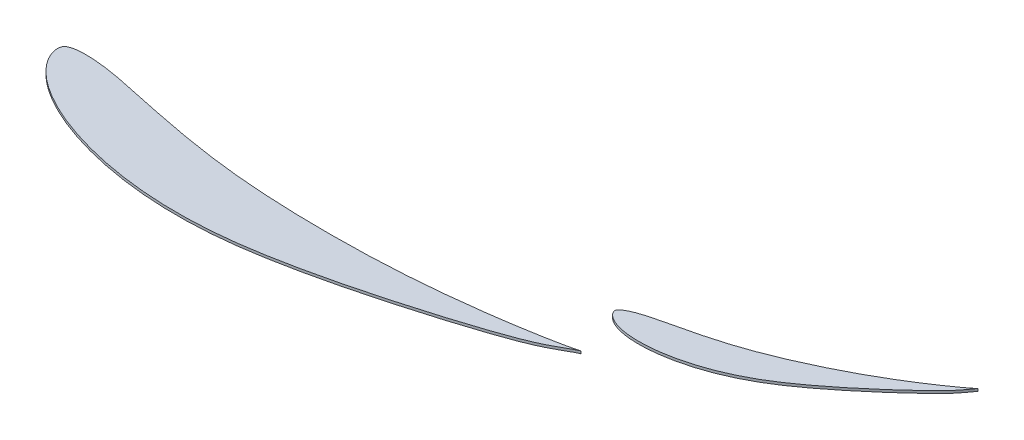
SolidWorks part; units mm, degrees
ref_plane "Front Plane" through (0, 0, 0) normal (0, 0, 1) x (1, 0, 0)
ref_plane "Top Plane" through (0, 0, 0) normal (0, 1, 0) x (1, 0, 0)
ref_plane "Right Plane" through (0, 0, 0) normal (1, 0, 0) x (0, 0, -1)
sketch "Sketch1" plane through (0, 0, 0) normal (0, 1, 0) x (1, 0, 0)
  spline S0 degree 3 poles (-69.7235, 37.8267) (-64.4975, 39.4817) (-69.3304, 37.4567) (-72.8148, 35.4) (-80.7227, 31.0375) (-89.8687, 26.058) (-101.6654, 20.7446) (-115.6887, 15.4124) (-131.9838, 9.7388) (-150.3138, 3.7512) (-170.4203, -2.4732) (-192.0007, -8.832) (-214.756, -15.1807) (-238.3766, -21.3821) (-262.5602, -27.2669) (-287.0162, -32.6385) (-311.4568, -37.3302) (-335.6828, -41.1008) (-359.5919, -43.6132) (-383.094, -44.823) (-406.1048, -44.7568) (-428.5003, -43.4674) (-450.1498, -41.0172) (-470.8999, -37.4937) (-490.597, -33.0546) (-509.0649, -27.8126) (-526.1291, -21.8663) (-541.6405, -15.3345) (-555.4661, -8.3369) (-567.501, -1.005) (-577.6561, 6.5208) (-585.8772, 14.0826) (-592.1333, 21.4997) (-596.4095, 28.5906) (-598.575, 34.6968) (-599.036, 38.9119) (-598.7904, 41.1263) (-598.5559, 42.2073) (-598.3073, 42.9095) (-598.0806, 43.4311) (-597.8794, 43.7859) (-597.6525, 44.1159) (-597.3684, 44.4079) (-597.0458, 44.6816) (-596.5563, 45.0558) (-595.837, 45.4763) (-594.6855, 46.0337) (-593.2668, 46.5595) (-589.5244, 47.655) (-582.5582, 48.4203) (-571.539, 48.2683) (-557.6787, 46.8029) (-540.9024, 44.032) (-521.0437, 39.934) (-497.9754, 34.8534) (-471.6859, 29.5034) (-442.4873, 24.3683) (-410.9191, 19.9029) (-377.6985, 16.6962) (-343.6903, 14.8703) (-309.6629, 14.1027) (-276.183, 14.2641) (-243.7578, 15.3066) (-212.9263, 17.2261) (-184.2105, 19.8361) (-158.0453, 22.8332) (-134.7326, 26.0011) (-114.6103, 29.1294) (-97.6267, 32.0949) (-84.6293, 34.5236) (-74.1006, 36.918) (-69.7235, 37.8267) (-64.4975, 39.4817) (-69.3304, 37.4567) knots -0.016237 -0.007308 -0.001841 0 0.001813 0.006911 0.014576 0.024172 0.035572 0.049013 0.064513 0.081849 0.100772 0.120997 0.142228 0.164173 0.186537 0.209023 0.231367 0.25332 0.274804 0.295858 0.316449 0.336531 0.356033 0.374893 0.39299 0.410197 0.426388 0.441459 0.455334 0.467938 0.479236 0.489204 0.497851 0.505194 0.511308 0.515097 0.516441 0.517273 0.51806 0.518436 0.518797 0.519154 0.519508 0.519887 0.520289 0.52116 0.522116 0.52372 0.525214 0.532575 0.542381 0.554776 0.569931 0.588005 0.609188 0.633329 0.660001 0.688743 0.718873 0.749543 0.780127 0.810209 0.839387 0.867183 0.893104 0.91676 0.937874 0.956199 0.971544 0.983763 0.992692 0.998159 1 1.001813 1.006911 1.014576 only from (-65.525, 39.1038) to (-65.525, 39.1038)
  spline S1 degree 3 poles (168.0228, 206.4477) (170.1374, 208.3902) (168.2914, 206.359) (167.0925, 204.6113) (164.3041, 200.7897) (161.0645, 196.4011) (156.6404, 191.2672) (151.1635, 185.6315) (144.6837, 179.3308) (137.3073, 172.4305) (129.14, 165.0246) (120.3027, 157.2285) (110.9055, 149.1773) (101.0648, 141.0043) (90.8868, 132.857) (80.4659, 124.8931) (69.9017, 117.2554) (59.2355, 110.1024) (48.4413, 103.6169) (37.5519, 97.8399) (26.6132, 92.7774) (15.696, 88.4318) (4.8758, 84.8024) (-5.755, 81.8816) (-16.0885, 79.6286) (-26.0162, 78.0289) (-35.4335, 77.0743) (-44.2432, 76.7413) (-52.3557, 77.0027) (-59.6922, 77.8192) (-66.1791, 79.1439) (-71.7559, 80.9138) (-76.3679, 83.0501) (-79.9676, 85.4697) (-82.3474, 87.8891) (-83.4994, 89.7882) (-83.873, 90.8938) (-84.0009, 91.4589) (-84.0384, 91.8473) (-84.0462, 92.1451) (-84.0292, 92.358) (-83.9946, 92.5649) (-83.9243, 92.7664) (-83.8318, 92.9678) (-83.6822, 93.2538) (-83.4339, 93.6127) (-83.0106, 94.1322) (-82.4535, 94.6958) (-80.9194, 96.0444) (-77.7817, 97.9498) (-72.5169, 100.317) (-65.6125, 102.6896) (-57.0349, 105.088) (-46.7001, 107.5387) (-34.6241, 110.2334) (-20.9593, 113.5133) (-5.961, 117.5393) (10.0139, 122.4077) (26.4947, 128.2394) (43.0437, 134.9011) (59.3676, 142.0694) (75.2258, 149.5575) (90.3884, 157.2304) (104.6002, 164.9669) (117.6547, 172.5628) (129.4127, 179.7778) (139.7787, 186.4425) (148.6389, 192.3821) (156.0451, 197.5496) (161.6777, 201.5798) (166.146, 205.0473) (168.0228, 206.4477) (170.1374, 208.3902) (168.2914, 206.359) knots -0.016237 -0.007308 -0.001841 0 0.001813 0.006911 0.014576 0.024172 0.035572 0.049013 0.064513 0.081849 0.100772 0.120997 0.142228 0.164173 0.186537 0.209023 0.231367 0.25332 0.274804 0.295858 0.316449 0.336531 0.356033 0.374893 0.39299 0.410197 0.426388 0.441459 0.455334 0.467938 0.479236 0.489204 0.497851 0.505194 0.511308 0.515097 0.516441 0.517273 0.51806 0.518436 0.518797 0.519154 0.519508 0.519887 0.520289 0.52116 0.522116 0.52372 0.525214 0.532575 0.542381 0.554776 0.569931 0.588005 0.609188 0.633329 0.660001 0.688743 0.718873 0.749543 0.780127 0.810209 0.839387 0.867183 0.893104 0.91676 0.937874 0.956199 0.971544 0.983763 0.992692 0.998159 1 1.001813 1.006911 1.014576 only from (169.7332, 207.9834) to (169.7332, 207.9834)
  dimension "D1" = 169.7332
  dimension "D2" = 65.525
  dimension "D3" = 39.1038
  dimension "D4" = 207.9834
extrude "Boss-Extrude1" add sketch "Sketch1" along normal blind 2.54
sketch "Sketch2" plane through (0, 2.54, 0) normal (0, 1, 0) x (1, 0, 0)
  spline S0 degree 3 poles (-69.3304, 37.4567) (-64.4975, 39.4817) (-69.7235, 37.8267) (-74.1006, 36.918) (-84.6293, 34.5236) (-97.6267, 32.0949) (-114.6103, 29.1294) (-134.7326, 26.0011) (-158.0453, 22.8332) (-184.2105, 19.8361) (-212.9263, 17.2261) (-243.7578, 15.3066) (-276.183, 14.2641) (-309.6629, 14.1027) (-343.6903, 14.8703) (-377.6985, 16.6962) (-410.9191, 19.9029) (-442.4873, 24.3683) (-471.6859, 29.5034) (-497.9754, 34.8534) (-521.0437, 39.934) (-540.9024, 44.032) (-557.6787, 46.8029) (-571.539, 48.2683) (-582.5582, 48.4203) (-589.5244, 47.655) (-593.2668, 46.5595) (-594.6855, 46.0337) (-595.837, 45.4763) (-596.5563, 45.0558) (-597.0458, 44.6816) (-597.3684, 44.4079) (-597.6525, 44.1159) (-597.8794, 43.7859) (-598.0806, 43.4311) (-598.3073, 42.9095) (-598.5559, 42.2073) (-598.7904, 41.1263) (-599.036, 38.9119) (-598.575, 34.6968) (-596.4095, 28.5906) (-592.1333, 21.4997) (-585.8772, 14.0826) (-577.6561, 6.5208) (-567.501, -1.005) (-555.4661, -8.3369) (-541.6405, -15.3345) (-526.1291, -21.8663) (-509.0649, -27.8126) (-490.597, -33.0546) (-470.8999, -37.4937) (-450.1498, -41.0172) (-428.5003, -43.4674) (-406.1048, -44.7568) (-383.094, -44.823) (-359.5919, -43.6132) (-335.6828, -41.1008) (-311.4568, -37.3302) (-287.0162, -32.6385) (-262.5602, -27.2669) (-238.3766, -21.3821) (-214.756, -15.1807) (-192.0007, -8.832) (-170.4203, -2.4732) (-150.3138, 3.7512) (-131.9838, 9.7388) (-115.6887, 15.4124) (-101.6654, 20.7446) (-89.8687, 26.058) (-80.7227, 31.0375) (-72.8148, 35.4) (-69.3304, 37.4567) (-64.4975, 39.4817) (-69.7235, 37.8267) knots -0.014576 -0.006911 -0.001813 0 0.001841 0.007308 0.016237 0.028456 0.043801 0.062126 0.08324 0.106896 0.132817 0.160613 0.189791 0.219873 0.250457 0.281127 0.311257 0.339999 0.366671 0.390812 0.411995 0.430069 0.445224 0.457619 0.467425 0.474786 0.47628 0.477884 0.47884 0.479711 0.480113 0.480492 0.480846 0.481203 0.481564 0.48194 0.482727 0.483559 0.484903 0.488692 0.494806 0.502149 0.510796 0.520764 0.532062 0.544666 0.558541 0.573612 0.589803 0.60701 0.625107 0.643967 0.663469 0.683551 0.704142 0.725196 0.74668 0.768633 0.790977 0.813463 0.835827 0.857772 0.879003 0.899228 0.918151 0.935487 0.950987 0.964428 0.975828 0.985424 0.993089 0.998187 1 1.001841 1.007308 1.016237 only from (-65.525, 39.1038) to (-65.525, 39.1038) construction
  spline S1 degree 3 poles (-69.3304, 37.4567) (-64.4975, 39.4817) (-69.7235, 37.8267) (-74.1006, 36.918) (-84.6293, 34.5236) (-97.6267, 32.0949) (-114.6103, 29.1294) (-134.7326, 26.0011) (-158.0453, 22.8332) (-184.2105, 19.8361) (-212.9263, 17.2261) (-243.7578, 15.3066) (-276.183, 14.2641) (-309.6629, 14.1027) (-343.6903, 14.8703) (-377.6985, 16.6962) (-410.9191, 19.9029) (-442.4873, 24.3683) (-471.6859, 29.5034) (-497.9754, 34.8534) (-521.0437, 39.934) (-540.9024, 44.032) (-557.6787, 46.8029) (-571.539, 48.2683) (-582.5582, 48.4203) (-589.5244, 47.655) (-593.2668, 46.5595) (-594.6855, 46.0337) (-595.837, 45.4763) (-596.5563, 45.0558) (-597.0458, 44.6816) (-597.3684, 44.4079) (-597.6525, 44.1159) (-597.8794, 43.7859) (-598.0806, 43.4311) (-598.3073, 42.9095) (-598.5559, 42.2073) (-598.7904, 41.1263) (-599.036, 38.9119) (-598.575, 34.6968) (-596.4095, 28.5906) (-592.1333, 21.4997) (-585.8772, 14.0826) (-577.6561, 6.5208) (-567.501, -1.005) (-555.4661, -8.3369) (-541.6405, -15.3345) (-526.1291, -21.8663) (-509.0649, -27.8126) (-490.597, -33.0546) (-470.8999, -37.4937) (-450.1498, -41.0172) (-428.5003, -43.4674) (-406.1048, -44.7568) (-383.094, -44.823) (-359.5919, -43.6132) (-335.6828, -41.1008) (-311.4568, -37.3302) (-287.0162, -32.6385) (-262.5602, -27.2669) (-238.3766, -21.3821) (-214.756, -15.1807) (-192.0007, -8.832) (-170.4203, -2.4732) (-150.3138, 3.7512) (-131.9838, 9.7388) (-115.6887, 15.4124) (-101.6654, 20.7446) (-89.8687, 26.058) (-80.7227, 31.0375) (-72.8148, 35.4) (-69.3304, 37.4567) (-64.4975, 39.4817) (-69.7235, 37.8267) knots -0.014576 -0.006911 -0.001813 0 0.001841 0.007308 0.016237 0.028456 0.043801 0.062126 0.08324 0.106896 0.132817 0.160613 0.189791 0.219873 0.250457 0.281127 0.311257 0.339999 0.366671 0.390812 0.411995 0.430069 0.445224 0.457619 0.467425 0.474786 0.47628 0.477884 0.47884 0.479711 0.480113 0.480492 0.480846 0.481203 0.481564 0.48194 0.482727 0.483559 0.484903 0.488692 0.494806 0.502149 0.510796 0.520764 0.532062 0.544666 0.558541 0.573612 0.589803 0.60701 0.625107 0.643967 0.663469 0.683551 0.704142 0.725196 0.74668 0.768633 0.790977 0.813463 0.835827 0.857772 0.879003 0.899228 0.918151 0.935487 0.950987 0.964428 0.975828 0.985424 0.993089 0.998187 1 1.001841 1.007308 1.016237 only from (-65.525, 39.1038) to (-65.525, 39.1038)
  spline S3 degree 3 poles (168.2914, 206.359) (170.1374, 208.3902) (168.0228, 206.4477) (166.146, 205.0473) (161.6777, 201.5798) (156.0451, 197.5496) (148.6389, 192.3821) (139.7787, 186.4425) (129.4127, 179.7778) (117.6547, 172.5628) (104.6002, 164.9669) (90.3884, 157.2304) (75.2258, 149.5575) (59.3676, 142.0694) (43.0437, 134.9011) (26.4947, 128.2394) (10.0139, 122.4077) (-5.961, 117.5393) (-20.9593, 113.5133) (-34.6241, 110.2334) (-46.7001, 107.5387) (-57.0349, 105.088) (-65.6125, 102.6896) (-72.5169, 100.317) (-77.7817, 97.9498) (-80.9194, 96.0444) (-82.4535, 94.6958) (-83.0106, 94.1322) (-83.4339, 93.6127) (-83.6822, 93.2538) (-83.8318, 92.9678) (-83.9243, 92.7664) (-83.9946, 92.5649) (-84.0292, 92.358) (-84.0462, 92.1451) (-84.0384, 91.8473) (-84.0009, 91.4589) (-83.873, 90.8938) (-83.4994, 89.7882) (-82.3474, 87.8891) (-79.9676, 85.4697) (-76.3679, 83.0501) (-71.7559, 80.9138) (-66.1791, 79.1439) (-59.6922, 77.8192) (-52.3557, 77.0027) (-44.2432, 76.7413) (-35.4335, 77.0743) (-26.0162, 78.0289) (-16.0885, 79.6286) (-5.755, 81.8816) (4.8758, 84.8024) (15.696, 88.4318) (26.6132, 92.7774) (37.5519, 97.8399) (48.4413, 103.6169) (59.2355, 110.1024) (69.9017, 117.2554) (80.4659, 124.8931) (90.8868, 132.857) (101.0648, 141.0043) (110.9055, 149.1773) (120.3027, 157.2285) (129.14, 165.0246) (137.3073, 172.4305) (144.6837, 179.3308) (151.1635, 185.6315) (156.6404, 191.2672) (161.0645, 196.4011) (164.3041, 200.7897) (167.0925, 204.6113) (168.2914, 206.359) (170.1374, 208.3902) (168.0228, 206.4477) knots -0.014576 -0.006911 -0.001813 0 0.001841 0.007308 0.016237 0.028456 0.043801 0.062126 0.08324 0.106896 0.132817 0.160613 0.189791 0.219873 0.250457 0.281127 0.311257 0.339999 0.366671 0.390812 0.411995 0.430069 0.445224 0.457619 0.467425 0.474786 0.47628 0.477884 0.47884 0.479711 0.480113 0.480492 0.480846 0.481203 0.481564 0.48194 0.482727 0.483559 0.484903 0.488692 0.494806 0.502149 0.510796 0.520764 0.532062 0.544666 0.558541 0.573612 0.589803 0.60701 0.625107 0.643967 0.663469 0.683551 0.704142 0.725196 0.74668 0.768633 0.790977 0.813463 0.835827 0.857772 0.879003 0.899228 0.918151 0.935487 0.950987 0.964428 0.975828 0.985424 0.993089 0.998187 1 1.001841 1.007308 1.016237 only from (169.7332, 207.9834) to (169.7332, 207.9834)
  spline S4 degree 3 poles (168.2914, 206.359) (170.1374, 208.3902) (168.0228, 206.4477) (166.146, 205.0473) (161.6777, 201.5798) (156.0451, 197.5496) (148.6389, 192.3821) (139.7787, 186.4425) (129.4127, 179.7778) (117.6547, 172.5628) (104.6002, 164.9669) (90.3884, 157.2304) (75.2258, 149.5575) (59.3676, 142.0694) (43.0437, 134.9011) (26.4947, 128.2394) (10.0139, 122.4077) (-5.961, 117.5393) (-20.9593, 113.5133) (-34.6241, 110.2334) (-46.7001, 107.5387) (-57.0349, 105.088) (-65.6125, 102.6896) (-72.5169, 100.317) (-77.7817, 97.9498) (-80.9194, 96.0444) (-82.4535, 94.6958) (-83.0106, 94.1322) (-83.4339, 93.6127) (-83.6822, 93.2538) (-83.8318, 92.9678) (-83.9243, 92.7664) (-83.9946, 92.5649) (-84.0292, 92.358) (-84.0462, 92.1451) (-84.0384, 91.8473) (-84.0009, 91.4589) (-83.873, 90.8938) (-83.4994, 89.7882) (-82.3474, 87.8891) (-79.9676, 85.4697) (-76.3679, 83.0501) (-71.7559, 80.9138) (-66.1791, 79.1439) (-59.6922, 77.8192) (-52.3557, 77.0027) (-44.2432, 76.7413) (-35.4335, 77.0743) (-26.0162, 78.0289) (-16.0885, 79.6286) (-5.755, 81.8816) (4.8758, 84.8024) (15.696, 88.4318) (26.6132, 92.7774) (37.5519, 97.8399) (48.4413, 103.6169) (59.2355, 110.1024) (69.9017, 117.2554) (80.4659, 124.8931) (90.8868, 132.857) (101.0648, 141.0043) (110.9055, 149.1773) (120.3027, 157.2285) (129.14, 165.0246) (137.3073, 172.4305) (144.6837, 179.3308) (151.1635, 185.6315) (156.6404, 191.2672) (161.0645, 196.4011) (164.3041, 200.7897) (167.0925, 204.6113) (168.2914, 206.359) (170.1374, 208.3902) (168.0228, 206.4477) knots -0.014576 -0.006911 -0.001813 0 0.001841 0.007308 0.016237 0.028456 0.043801 0.062126 0.08324 0.106896 0.132817 0.160613 0.189791 0.219873 0.250457 0.281127 0.311257 0.339999 0.366671 0.390812 0.411995 0.430069 0.445224 0.457619 0.467425 0.474786 0.47628 0.477884 0.47884 0.479711 0.480113 0.480492 0.480846 0.481203 0.481564 0.48194 0.482727 0.483559 0.484903 0.488692 0.494806 0.502149 0.510796 0.520764 0.532062 0.544666 0.558541 0.573612 0.589803 0.60701 0.625107 0.643967 0.663469 0.683551 0.704142 0.725196 0.74668 0.768633 0.790977 0.813463 0.835827 0.857772 0.879003 0.899228 0.918151 0.935487 0.950987 0.964428 0.975828 0.985424 0.993089 0.998187 1 1.001841 1.007308 1.016237 only from (169.7332, 207.9834) to (169.7332, 207.9834)
  dimension "D1" = 0
